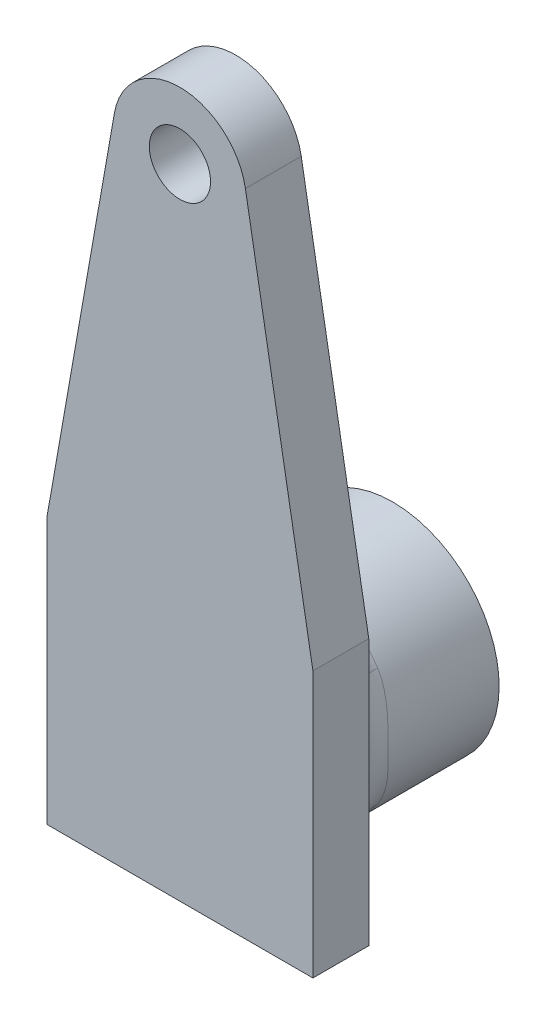
SolidWorks part; units mm, degrees
material "ABS"
ref_plane "Front Plane" through (0, 0, 0) normal (0, 0, 1) x (1, 0, 0)
ref_plane "Top Plane" through (0, 0, 0) normal (0, 1, 0) x (1, 0, 0)
ref_plane "Right Plane" through (0, 0, 0) normal (1, 0, 0) x (0, 0, -1)
sketch "Sketch1" plane through (0, 0, 0) normal (0, 0, 1) x (1, 0, 0)
  line L0 (0, -5) -> (0, 5) construction
  line L1 (-5, -5) -> (5, -5)
  line L2 (-5, -5) -> (-5, 5)
  line L3 (-5, 5) -> (5, 5) construction
  line L4 (5, -5) -> (5, 5)
  line L5 (-5, 5) -> (-2.4622, 19.4329)
  line L6 (5, 5) -> (2.4622, 19.4329)
  arc A0 (-2.4622, 19.4329) -> (2.4622, 19.4329) centre (0, 19) cw
  circle A1 centre (0, 19) radius 1.15
  dimension "D2" = 2.5
  dimension "D3" = 24
  dimension "D4" = 2.3
  dimension "D1" = 10
extrude "Boss-Extrude1" add sketch "Sketch1" along normal blind 2.1
ref_axis "Axis1" through (0, 0, -0.105) along (0, 0, 1)
sketch "Sketch2" plane through (0, 0, 0) normal (0, 0, -1) x (-1, 0, 0)
  circle A0 centre (0, 0) radius 4
  circle A1 centre (0, 0) radius 3
  dimension "D1" = 8
  dimension "D2" = 6
extrude "Boss-Extrude2" add sketch "Sketch2" along normal blind 5.9
fillet "Fillet1" radius 2 1 edges at (-4, 0, 0)
